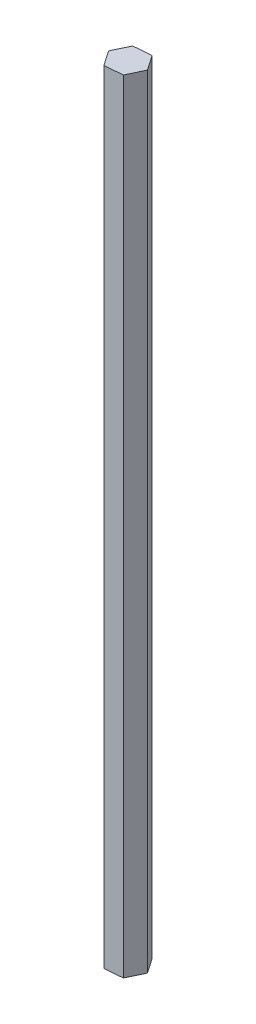
SolidWorks part; units mm, degrees
material "ALUMINUM 6061-T6"
ref_plane "Front Plane" through (0, 0, 0) normal (0, 0, 1) x (1, 0, 0)
ref_plane "Top Plane" through (0, 0, 0) normal (0, 1, 0) x (1, 0, 0)
ref_plane "Right Plane" through (0, 0, 0) normal (1, 0, 0) x (0, 0, -1)
sketch "Sketch1" plane through (0, 0, 0) normal (0, 1, 0) x (1, 0, 0)
  line L1 (7.3114, 0.554) -> (3.1759, 6.6089)
  line L2 (3.1759, 6.6089) -> (-4.1355, 6.0548)
  line L3 (-4.1355, 6.0548) -> (-7.3114, -0.554)
  line L4 (-7.3114, -0.554) -> (-3.1759, -6.6089)
  line L5 (-3.1759, -6.6089) -> (4.1355, -6.0548)
  line L6 (4.1355, -6.0548) -> (7.3114, 0.554)
  circle A1 centre (0, 0) radius 6.35 construction
extrude "Boss-Extrude1" add sketch "Sketch1" along normal mid plane 317.5
ref_axis "Axis1" through (0, -167.64, 0) along (0, 1, 0)
